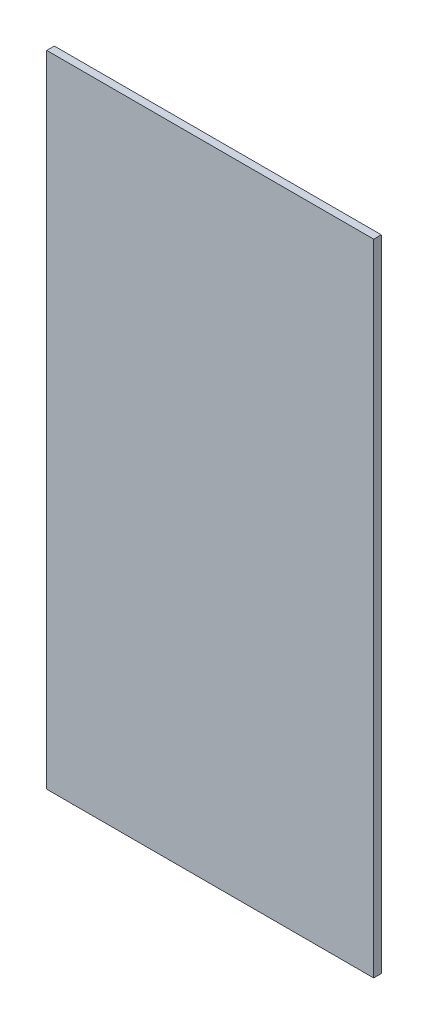
SolidWorks part; units mm, degrees
ref_plane "Front" through (0, 0, 0) normal (0, 0, 1) x (1, 0, 0)
ref_plane "Top" through (0, 0, 0) normal (0, 1, 0) x (1, 0, 0)
ref_plane "Right" through (0, 0, 0) normal (1, 0, 0) x (0, 0, -1)
sketch "Sketch1" plane through (0, 0, 0) normal (0, 0, 1) x (1, 0, 0)
  line L1 (0, 0) -> (258.57, 0)
  line L2 (0, 0) -> (0, 506)
  line L3 (0, 506) -> (258.57, 506)
  line L4 (258.57, 0) -> (258.57, 506)
  dimension "D1" = 258.57
  dimension "D2" = 506
extrude "Boss-Extrude1" add sketch "Sketch1" along normal blind 6
